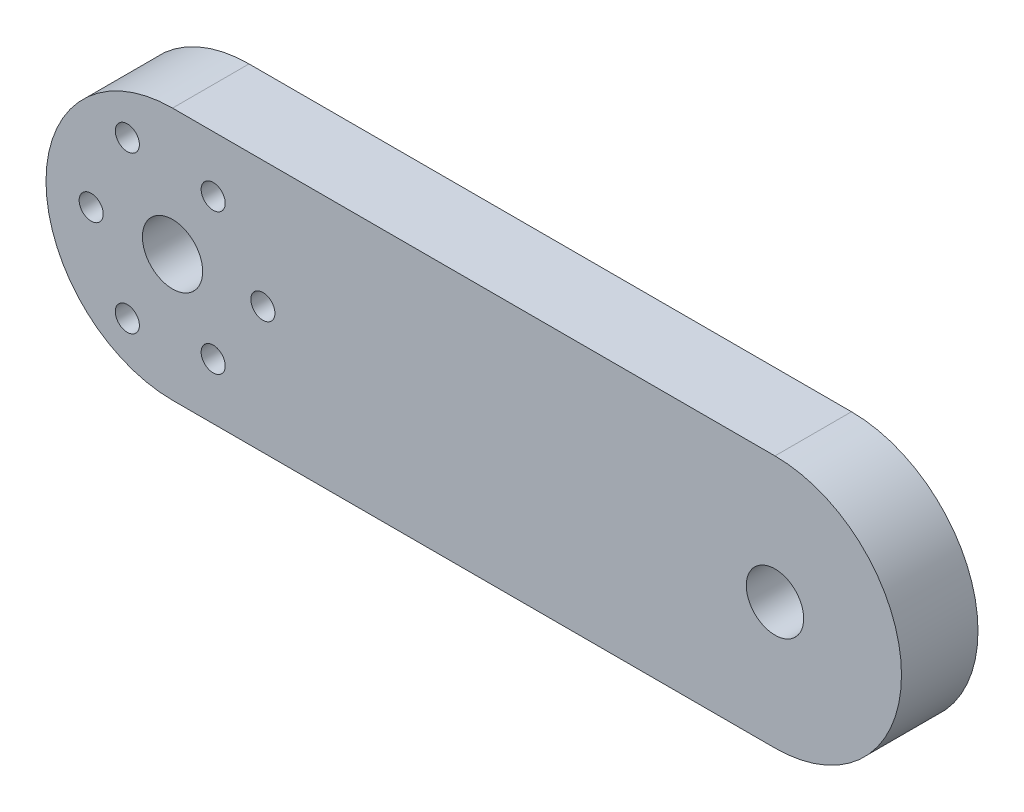
SolidWorks part; units mm, degrees
material "Alloy Steel"
ref_plane "Front Plane" through (0, 0, 0) normal (0, 0, 1) x (1, 0, 0)
ref_plane "Top Plane" through (0, 0, 0) normal (0, 1, 0) x (1, 0, 0)
ref_plane "Right Plane" through (0, 0, 0) normal (1, 0, 0) x (0, 0, -1)
sketch "Sketch1" plane through (0, 0, 0) normal (0, 0, 1) x (1, 0, 0)
  line L0 (0, 0) -> (100, 0) construction
  line L1 (0, 21) -> (100, 21)
  line L2 (0, -21) -> (100, -21)
  arc A1 (0, 21) -> (0, -21) centre (0, 0) ccw
  arc A2 (100, -21) -> (100, 21) centre (100, 0) ccw
  circle A3 centre (100, 0) radius 4.7625
  circle A4 centre (0, 0) radius 15 construction
  circle A5 centre (15, 0) radius 2
  circle A6 centre (-7.5, -12.9904) radius 2
  circle A7 centre (-7.5, 12.9904) radius 2
  circle A8 centre (0, 0) radius 5
  circle A9 centre (0, 0) radius 13.5 construction
  circle A10 centre (-13.5, 0) radius 2
  circle A11 centre (6.75, 11.6913) radius 2
  circle A12 centre (6.75, -11.6913) radius 2
  point P3 (50, 0)
  point P20 (0, 0)
  point P29 (0, 0)
  dimension "D1" = 9.525
  dimension "D2" = 30
  dimension "D3" = 4
  dimension "D5" = 10
  dimension "D6" = 27
  dimension "D7" = 4
  dimension "D4" = 3
  dimension "D8" = 3
extrude "Boss-Extrude2" add sketch "Sketch1" along normal blind 12.7
